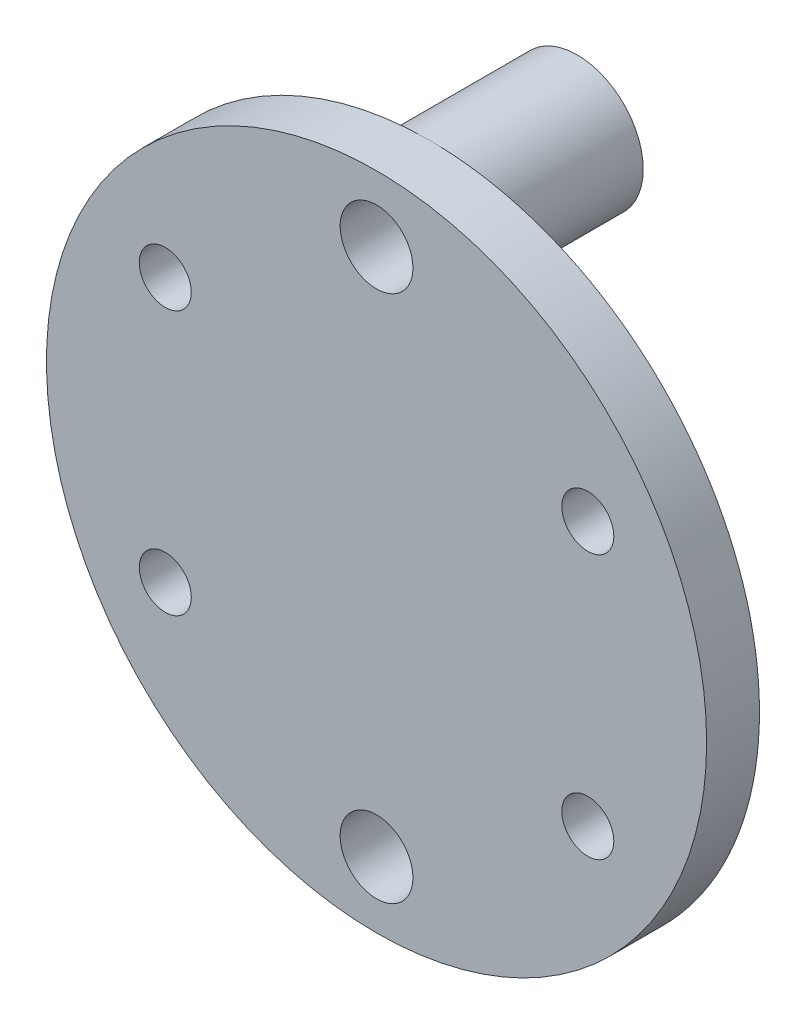
SolidWorks part; units mm, degrees
material "PLA"
ref_plane "Front Plane" through (0, 0, 0) normal (0, 0, 1) x (1, 0, 0)
ref_plane "Top Plane" through (0, 0, 0) normal (0, 1, 0) x (1, 0, 0)
ref_plane "Right Plane" through (0, 0, 0) normal (1, 0, 0) x (0, 0, -1)
sketch "Sketch1" plane through (0, 0, 0) normal (0, 0, 1) x (1, 0, 0)
  line L0 (0, 0) -> (5.8527, 0) construction
  line L1 (0, 0) -> (0, 4.6978) construction
  circle A0 centre (0, 0) radius 15.875
  circle A1 centre (0, 12.7) radius 1.75
  circle A2 centre (0, 12.7) radius 3.175
  circle A3 centre (0, -12.7) radius 1.75
  circle A4 centre (0, -12.7) radius 3.175
  circle A5 centre (-10.16, 6.35) radius 1.25
  circle A6 centre (10.16, 6.35) radius 1.25
  circle A7 centre (10.16, -6.35) radius 1.25
  circle A8 centre (-10.16, -6.35) radius 1.25
  dimension "D1" = 31.75
  dimension "D2" = 3.5
  dimension "D4" = 2.5
  dimension "D3" = 12.7
  dimension "D5" = 12.7
  dimension "D6" = 20.32
extrude "Boss-Extrude1" add sketch "Sketch1" along normal blind 2.54 contours A0 A4 A2 A6 A5 A7 A8 | A2 A1 | A4 A3 region at (2.1816, 14.8816, 0) region at (-2.1816, -10.5184, 0) region at (0, 0, 0)
extrude "Boss-Extrude2" add sketch "Sketch1<3>" against normal blind 7.11 contours A2 A1 | A4 A3 region at (2.1816, 14.8816, 0) region at (-2.1816, -10.5184, 0)
sketch "Sketch1<3>" plane through (0, 0, 0) normal (0, 0, 1) x (1, 0, 0) same geometry as "Sketch1"
